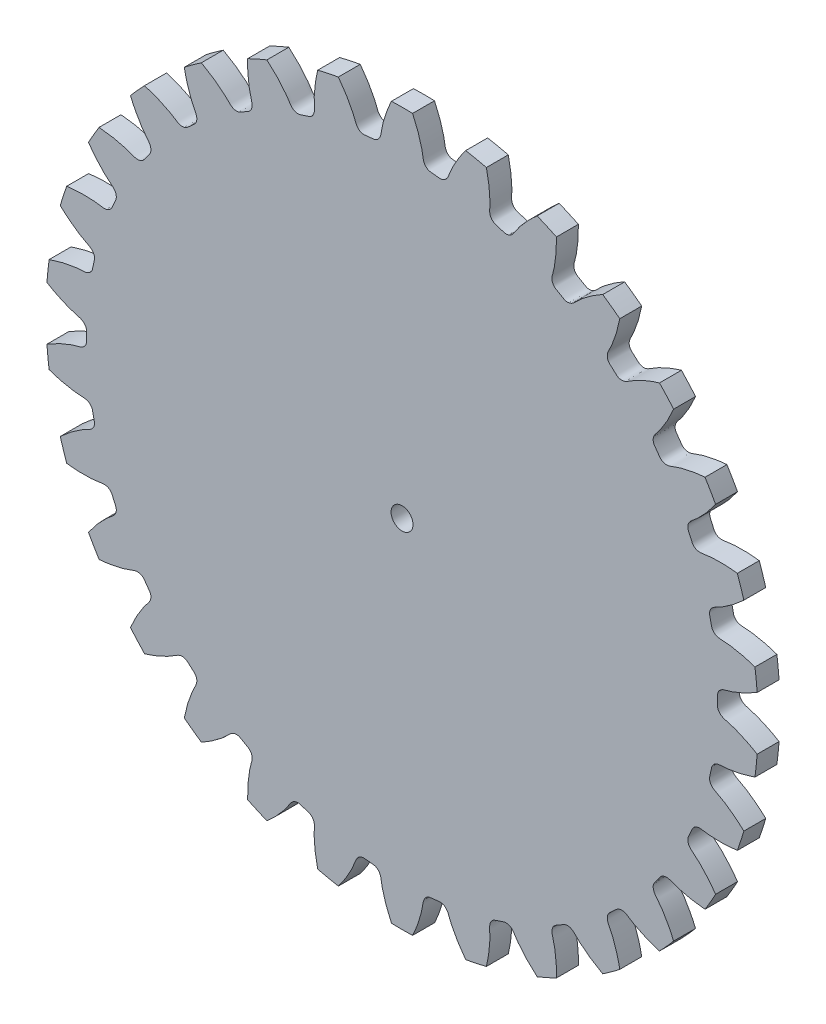
SolidWorks part; units mm, degrees
ref_plane "Front Plane" through (0, 0, 0) normal (0, 0, 1) x (1, 0, 0)
ref_plane "Top Plane" through (0, 0, 0) normal (0, 1, 0) x (1, 0, 0)
ref_plane "Right Plane" through (0, 0, 0) normal (1, 0, 0) x (0, 0, -1)
ref_axis "Axis1" through (0, 0, 55) along (0, 0, -1)
sketch "SketchRevolveGeartrax1Gear" plane through (0, 0, 0) normal (1, 0, 0) x (0, 0, -1)
  line L0 (0, 0) -> (1, 0) construction
  line L1 (-4, 0) -> (-4, 129.945)
  line L2 (-4, 129.945) -> (4, 129.945)
  line L3 (4, 129.945) -> (4, 0)
  line L4 (4, 0) -> (-4, 0)
  dimension "Side1" = 4
  dimension "OutsideRadius" = 129.945
  dimension "Side2" = 4
revolve "Geartrax1Gear" add sketch "SketchRevolveGeartrax1Gear" angle 360 about L0
sketch "SketchToothGeartrax1Gear" plane through (0, 0, 0) normal (0, 0, 1) x (1, 0, 0)
  arc A0 (129.894, 9.9432) -> (129.894, -9.9432) centre (0, 0) cw
  spline S0 degree 3 poles (129.894, -9.9432) (129.0232, -9.4093) (127.866, -8.7397) (126.4176, -7.9731) (125.6085, -7.5634) (124.8265, -7.1852) (124.0724, -6.8371) (123.3471, -6.5182) (122.6513, -6.2272) (121.9859, -5.963) (121.3515, -5.7243) (120.7489, -5.51) (120.1787, -5.3188) (119.6416, -5.1493) (119.1379, -5.001) (118.4579, -4.8106) (117.868, -4.6835) (117.3845, -4.5169) (117.1837, -4.4387) (116.982, -4.3493) (116.7778, -4.2461) (116.569, -4.1248) (116.3539, -3.9799) (116.1317, -3.8036) (115.9035, -3.5855) (115.6745, -3.3134) (115.4571, -2.9752) (115.2735, -2.5643) (115.1539, -2.1034) (115.1032, -1.2389) (115.1705, 0) (115.1032, 1.2389) (115.1539, 2.1034) (115.2735, 2.5643) (115.4571, 2.9752) (115.6745, 3.3134) (115.9035, 3.5855) (116.1317, 3.8036) (116.3539, 3.9799) (116.569, 4.1248) (116.7778, 4.2461) (116.982, 4.3493) (117.1837, 4.4387) (117.3845, 4.5169) (117.868, 4.6835) (118.4579, 4.8106) (119.1379, 5.001) (119.6416, 5.1493) (120.1787, 5.3188) (120.7489, 5.51) (121.3515, 5.7243) (121.9859, 5.963) (122.6513, 6.2272) (123.3471, 6.5182) (124.0724, 6.8371) (124.8265, 7.1852) (125.6085, 7.5634) (126.4176, 7.9731) (127.866, 8.7397) (129.0232, 9.4093) (129.894, 9.9432) knots 0 0 0 0 0.079652 0.104218 0.127792 0.150373 0.171961 0.192557 0.212161 0.230771 0.248389 0.265015 0.280648 0.295288 0.308936 0.321591 0.350362 0.355881 0.361459 0.367162 0.373074 0.379301 0.38598 0.393279 0.401398 0.410557 0.420947 0.432651 0.445522 0.457824 0.5 0.542176 0.554478 0.567349 0.579053 0.589443 0.598602 0.606721 0.61402 0.620699 0.626926 0.632838 0.638541 0.644119 0.649638 0.678409 0.691064 0.704712 0.719352 0.734985 0.751611 0.769229 0.787839 0.807443 0.828039 0.849627 0.872208 0.895782 0.920348 1 1 1 1
extrude "ToothExtrudeCutGeartrax1Gear" cut sketch "SketchToothGeartrax1Gear" against normal blind 4 and the other way blind 4
pattern_circular "PatternGeartrax1Gear" count 30 every 12 about axis through (0, 0, 55) along (0, 0, -1) of "ToothExtrudeCutGeartrax1Gear"
sketch "BoreRevolveSketch" plane through (0, 0, 0) normal (1, 0, 0) x (0, 0, -1)
  line L0 (0, 0) -> (1, 0) construction
  line L1 (-4, 0) -> (4, 0)
  line L2 (4, 0) -> (4, 4)
  line L3 (4, 4) -> (-4, 4)
  line L4 (-4, 4) -> (-4, 0)
  dimension "BoreSide1" = 4
  dimension "TaperSide1" = 4
  dimension "BoreSide2" = 4
  dimension "TaperSide2" = 4
revolve "BoreRevolveCut" cut sketch "BoreRevolveSketch" angle 360 about L0
sketch "AuxiliarySketchGeartrax1Gear" plane through (0, 0, 0) normal (0, 0, 1) x (1, 0, 0)
  circle A0 centre (0, 0) radius 123.3655 construction
  circle A1 centre (0, 0) radius 115.9257 construction
  circle A2 centre (0, 0) radius 118.1646 construction
  circle A3 centre (0, 0) radius 129.945 construction
  circle A4 centre (0, 0) radius 115.1411 construction
  dimension "PitchDiameter" = 246.731
  dimension "BaseDiameter" = 231.8513
  dimension "FormDiameter" = 236.3292
  dimension "MajorDiameter" = 259.89
  dimension "MinorDiameter" = 230.2823
